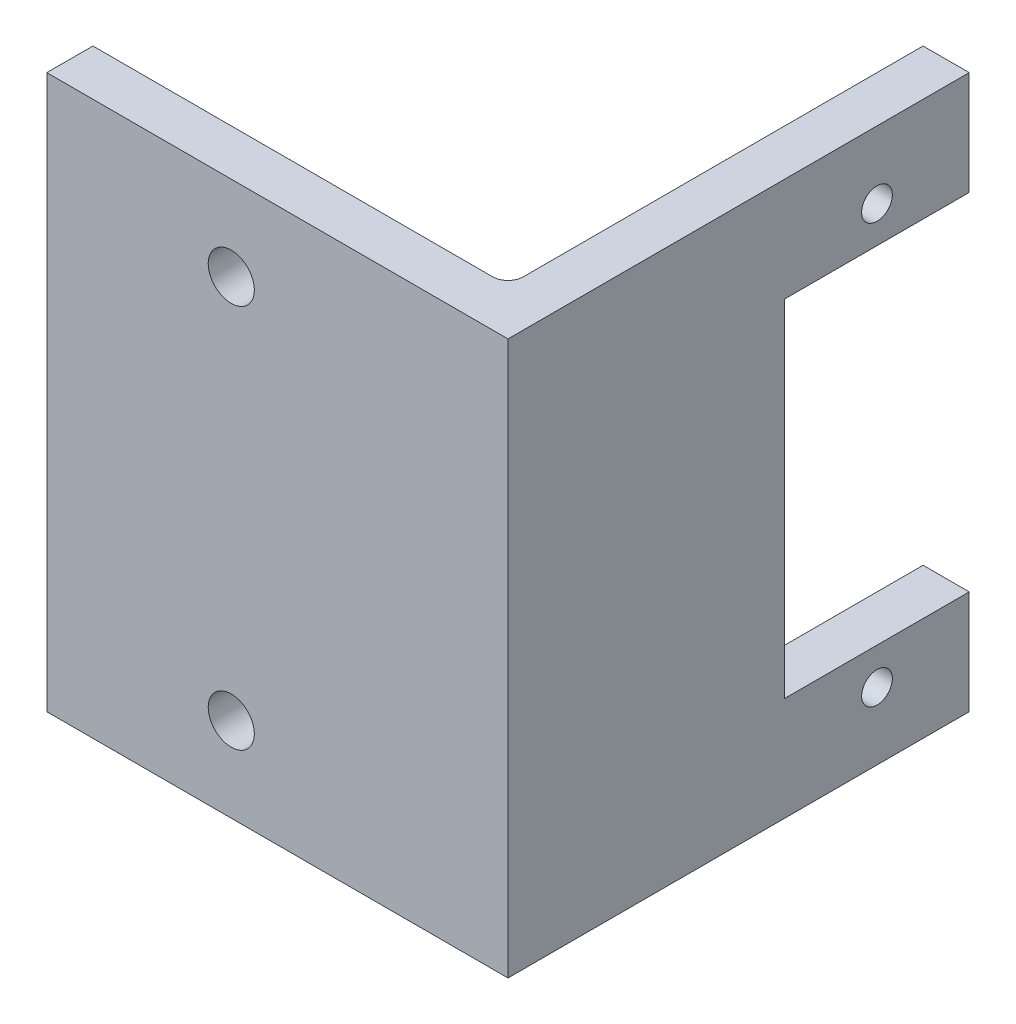
SolidWorks part; units mm, degrees
ref_plane "Front Plane" through (0, 0, 0) normal (0, 0, 1) x (1, 0, 0)
ref_plane "Top Plane" through (0, 0, 0) normal (0, 1, 0) x (1, 0, 0)
ref_plane "Right Plane" through (0, 0, 0) normal (1, 0, 0) x (0, 0, -1)
sketch "Sketch1" plane through (0, 0, 0) normal (0, 1, 0) x (1, 0, 0)
  line L0 (0, 0) -> (0, 30)
  line L1 (0, 0) -> (-30, 0)
  dimension "D1" = 30
extrude "Extrude-Thin1" add sketch "Sketch1" along normal mid plane 36 thin thin type one direction wall 3
sketch "Sketch2" plane through (0, 0, 0) normal (1, 0, 0) x (0, 0, -1)
  line L0 (0, 0) -> (36.7713, 0) construction
  line L1 (30, 18) -> (30, -18) construction
  line L2 (18, 11.25) -> (30, 11.25)
  line L3 (18, 11.25) -> (18, -11.25)
  line L4 (18, -11.25) -> (30, -11.25)
  line L5 (30, 11.25) -> (30, -11.25)
  line L6 (18, 11.25) -> (30, -11.25) construction
  line L7 (18, -11.25) -> (30, 11.25) construction
  line L8 (24, 13.625) -> (24, -13.625) construction
  circle A0 centre (24, 13.625) radius 1
  circle A1 centre (24, -13.625) radius 1
  point P3 (24, 0)
  point P14 (0, 0)
  point P15 (0, 0)
  dimension "D3" = 2
  dimension "D1" = 12
  dimension "D2" = 22.5
  dimension "D4" = 27.25
extrude "Cut-Extrude1" cut sketch "Sketch2" against normal blind 10
sketch "Sketch3" plane through (0, 0, -3) normal (0, 0, -1) x (-1, 0, 0)
  line L0 (3, 18) -> (3, -18) construction
  line L1 (3, 2) -> (25, 2)
  line L2 (3, 2) -> (3, -2)
  line L3 (3, -2) -> (25, -2)
  line L4 (25, 2) -> (25, -2)
  line L5 (0, 0) -> (43.5118, 0) construction
  dimension "D1" = 22
  dimension "D2" = 4
extrude "Boss-Extrude1" add sketch "Sketch3" along normal blind 15
sketch "Sketch4" plane through (0, 2, 0) normal (0, 1, 0) x (1, 0, 0)
  line L0 (-25, 3) -> (-10, 18)
  line L1 (-25, 18) -> (-3, 18) construction
  line L2 (-10, 18) -> (-25, 18)
  line L3 (-25, 18) -> (-25, 3)
  dimension "D1" = 15
extrude "Cut-Extrude2" cut sketch "Sketch4" against normal blind 15
fillet "Fillet1" radius 1 4 edges at (-3, -2, -10.5) (-17.5, -2, -10.5) (-3, 2, -10.5) (-17.5, 2, -10.5)
fillet "Fillet2" radius 1 9 edges at (-3, -10.5, -3) (-3.2929, -2.2929, -3) (-13.7929, -2, -3) (-24.5858, -1.7071, -3) (-25, 0, -3) (-24.5858, 1.7071, -3) (-13.7929, 2, -3) (-3.2929, 2.2929, -3) (-3, 10.5, -3)
sketch "Sketch5" plane through (0, 0, -3) normal (0, 0, -1) x (-1, 0, 0)
  line L0 (0, 0) -> (35.4788, 0) construction
  line L1 (18, -12.5) -> (18, 12.5) construction
  line L2 (30, 18) -> (30, -18) construction
  circle A0 centre (18, -12.5) radius 1.5
  circle A1 centre (18, 12.5) radius 1.5
  dimension "D1" = 3
  dimension "D2" = 12
  dimension "D3" = 25
extrude "Cut-Extrude3" cut sketch "Sketch5" against normal blind 15
